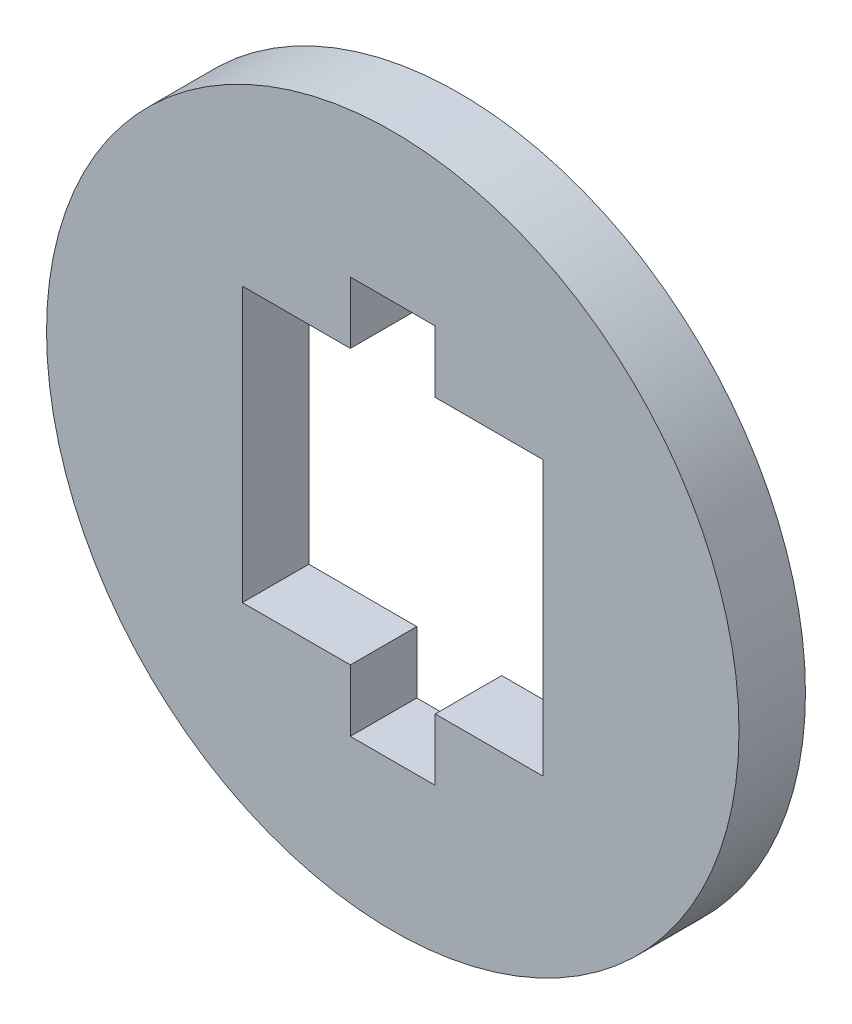
SolidWorks part; units mm, degrees
ref_plane "Front Plane" through (0, 0, 0) normal (0, 0, 1) x (1, 0, 0)
ref_plane "Top Plane" through (0, 0, 0) normal (0, 1, 0) x (1, 0, 0)
ref_plane "Right Plane" through (0, 0, 0) normal (1, 0, 0) x (0, 0, -1)
sketch "Sketch1" plane through (0, 0, 0) normal (0, 0, 1) x (1, 0, 0)
  circle A0 centre (0, 0) radius 52.1051
extrude "Boss-Extrude1" add sketch "Sketch1" along normal blind 10
sketch "Sketch2" plane through (0, 0, 10) normal (0, 0, 1) x (1, 0, 0)
  line L1 (-22.6318, -20.6242) -> (22.6318, -20.6242)
  line L2 (-22.6318, -20.6242) -> (-22.6318, 20.6242)
  line L3 (-22.6318, 20.6242) -> (22.6318, 20.6242)
  line L4 (22.6318, -20.6242) -> (22.6318, 20.6242)
  line L5 (-22.6318, -20.6242) -> (22.6318, 20.6242) construction
  line L6 (-22.6318, 20.6242) -> (22.6318, -20.6242) construction
  point P0 (0, 0)
extrude "Cut-Extrude1" cut sketch "Sketch2" against normal through all
sketch "Sketch3" plane through (0, 0, 10) normal (0, 0, 1) x (1, 0, 0)
  line L1 (-6.388, -29.9324) -> (6.388, -29.9324)
  line L2 (-6.388, -29.9324) -> (-6.388, 29.9324)
  line L3 (-6.388, 29.9324) -> (6.388, 29.9324)
  line L4 (6.388, -29.9324) -> (6.388, 29.9324)
  line L5 (-6.388, -29.9324) -> (6.388, 29.9324) construction
  line L6 (-6.388, 29.9324) -> (6.388, -29.9324) construction
  point P0 (0, 0)
extrude "Cut-Extrude2" cut sketch "Sketch3" against normal through all
